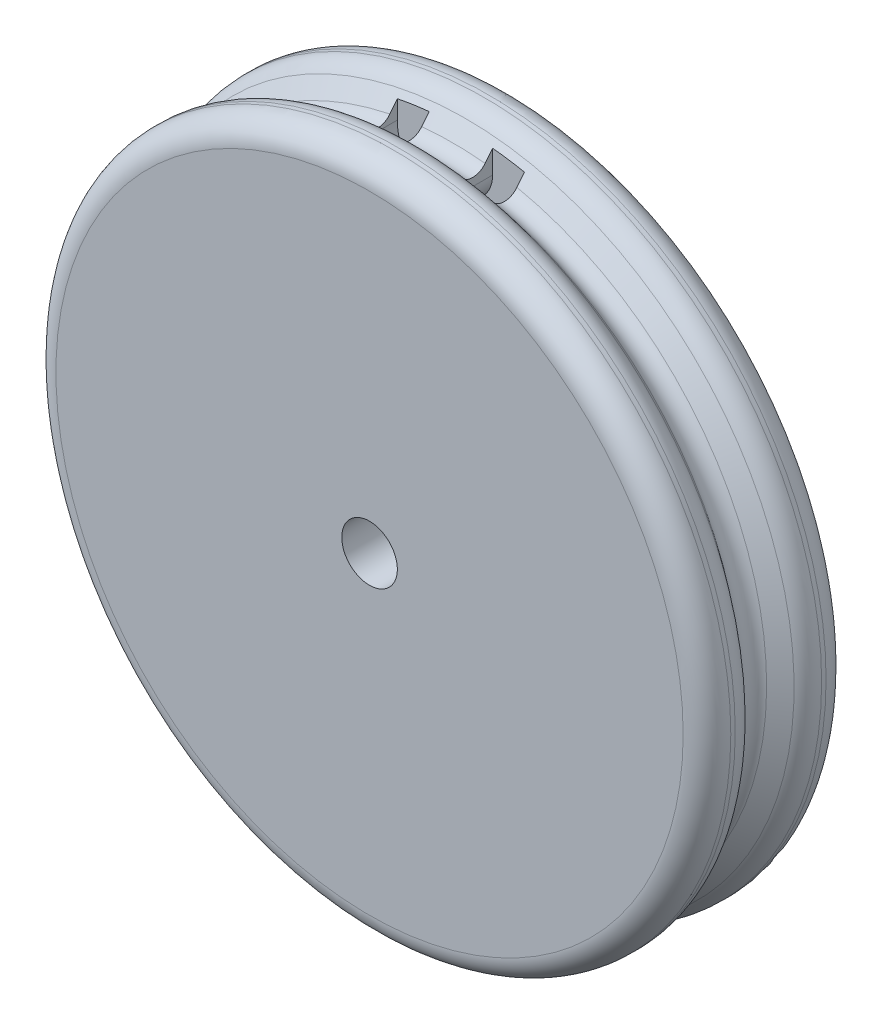
SolidWorks part; units mm, degrees
ref_plane "Front Plane" through (0, 0, 0) normal (0, 0, 1) x (1, 0, 0)
ref_plane "Top Plane" through (0, 0, 0) normal (0, 1, 0) x (1, 0, 0)
ref_plane "Right Plane" through (0, 0, 0) normal (1, 0, 0) x (0, 0, -1)
sketch "Sketch1" plane through (0, 0, 0) normal (0, 0, 1) x (1, 0, 0)
  circle A0 centre (0, 0) radius 37.5
  dimension "D1" = 75
extrude "Boss-Extrude1" add sketch "Sketch1" along normal mid plane 8
sketch "Sketch2" plane through (0, 0, 4) normal (0, 0, 1) x (1, 0, 0)
  circle A0 centre (0, 0) radius 42.5
  dimension "D1" = 85
extrude "Boss-Extrude2" add sketch "Sketch2" along normal blind 5
sketch "Sketch6" plane through (0, 0, 0) normal (1, 0, 0) x (0, 0, -1)
  line L0 (-4, 42.5) -> (0, 37.5)
  line L1 (4, 37.5) -> (-4, 37.5) construction
  line L2 (0, 37.5) -> (-4, 37.5)
  line L3 (-4, 37.5) -> (-4, 42.5)
  line L4 (-30.4204, 0) -> (21.2132, 0) construction
revolve "Revolve1" add sketch "Sketch6" angle 360 about L4
mirror "Mirror1" about plane through (0, 0, 0) normal (0, 0, 1) of "Revolve1", "Boss-Extrude2"
ref_plane "Plane3" through (0, 0, 0) normal (0, 0, 1) x (1, 0, 0)
sketch "Sketch7" plane through (0, 0, 0) normal (0, 0, 1) x (1, 0, 0)
  line L0 (0, 37.5) -> (0, -42.5) construction
  line L3 (-4, 37.5) -> (-4, 42.3113)
  line L4 (-8, 37.5) -> (-8, 41.7403)
  line L5 (0, 37.5) -> (15.7968, 37.5) construction
  line L6 (4, 37.5) -> (4, 42.3113)
  line L7 (8, 37.5) -> (8, 41.7403)
  arc A2 (-4, 37.5) -> (4, 37.5) centre (0, 37.5) ccw
  arc A3 (-8, 37.5) -> (8, 37.5) centre (0, 37.5) ccw
  circle A6 centre (0, 0) radius 42.5 construction
  arc A7 (8, 41.7403) -> (4, 42.3113) centre (0, 0) ccw
  arc A8 (-4, 42.3113) -> (-8, 41.7403) centre (0, 0) ccw
  circle A9 centre (0, 0) radius 42.5 construction
  circle A10 centre (0, 0) radius 42.5 construction
  point P1 (0, -42.5)
  point P13 (4.5078, 42.2603)
  point P18 (0, 0)
  point P21 (0, 0)
  point P22 (4.5078, 42.2603)
  point P23 (-4.5078, 42.2603)
  point P24 (-7.9839, 36.9929)
  point P25 (-8.697, 41.6006)
  point P26 (5.3435, 42.2603)
  point P27 (-4.5078, 42.1643)
  point P28 (-4, 42.3113)
  point P29 (-8, 41.7403)
  point P30 (4, 42.3113)
  point P31 (7.9839, 41.7433)
  point P32 (8, 37.5)
  point P33 (0, 0)
  point P34 (0, 0)
  dimension "D1" = 4
  dimension "D2" = 8
  dimension "D3" = 37.5
extrude "Cut-Extrude4" cut sketch "Sketch7" against normal mid plane 5
sketch "Sketch4" plane through (0, 0, -9) normal (0, 0, -1) x (-1, 0, 0)
  circle A0 centre (0, 0) radius 3.5
  dimension "D1" = 7
extrude "Cut-Extrude3" cut sketch "Sketch4" against normal through all
fillet "Fillet2" radius 2 2 edges at (0, 37.5, 0) (0, -37.5, 0)
fillet "Fillet3" radius 3 4 edges at (42.5, 0, -4) (42.5, 0, 4) (42.5, 0, 9) (42.5, 0, -9)
